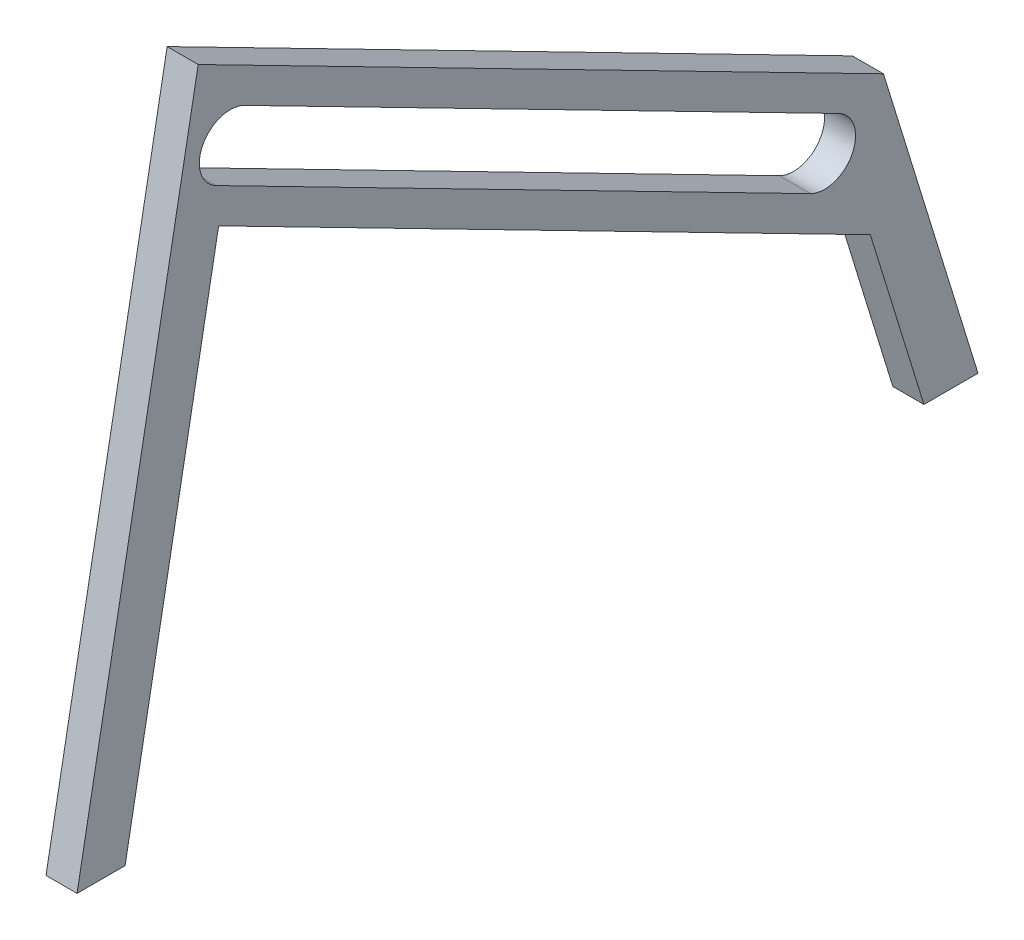
SolidWorks part; units mm, degrees
ref_plane "Front Plane" through (0, 0, 0) normal (0, 0, 1) x (1, 0, 0)
ref_plane "Top Plane" through (0, 0, 0) normal (0, 1, 0) x (1, 0, 0)
ref_plane "Right Plane" through (0, 0, 0) normal (1, 0, 0) x (0, 0, -1)
sketch "Sketch1" plane through (0, 0, 0) normal (1, 0, 0) x (0, 0, -1)
  line L0 (-444.5, 0) -> (444.5, 0) construction
  line L1 (-444.5, 0) -> (-394.9465, 268.859) construction
  line L2 (-394.9465, 268.859) -> (-444.5, 0)
  line L3 (-394.9465, 268.859) -> (-114.6521, 125.4156)
  line L4 (-394.9465, 268.859) -> (-394.9465, 0) construction
  line L9 (-114.6521, 125.4156) -> (-75.9791, 0)
  line L10 (-254.7993, 197.1373) -> (-306.6298, 95.8584) construction
  line L16 (-306.6298, 95.8584) -> (-454.2509, 171.4049) construction
  line L17 (-306.6298, 95.8584) -> (-85.4714, -17.3216) construction
  line L18 (-394.9465, 0) -> (-394.9465, -231.14) construction
  line L19 (-260.585, 185.8317) -> (-302.8069, 207.4392) construction
  line L20 (-272.1565, 163.2207) -> (-316.6941, 186.0132) construction
  line L21 (-277.9422, 151.9151) -> (-386.5959, 207.5197)
  line L22 (-277.9422, 151.9151) -> (-120.015, 71.0943)
  line L23 (-419.7233, 134.4295) -> (-381.7028, 127.4219) construction
  line L24 (-400.713, 130.9257) -> (-424.844, 0) construction
  line L25 (-400.713, 130.9257) -> (-386.5959, 207.5197) construction
  line L26 (-386.5959, 207.5197) -> (-424.844, 0)
  line L27 (-98.0924, 0) -> (-120.015, 71.0943)
  line L28 (-293.905, 202.8836) -> (-305.4765, 180.2725) construction
  line L29 (-299.6907, 191.578) -> (-381.7903, 233.5933) construction
  line L30 (-299.6907, 191.578) -> (-138.7539, 109.2171) construction
  line L31 (-381.7903, 233.5933) -> (-138.7539, 109.2171) construction
  line L32 (-376.0046, 244.8988) -> (-132.9682, 120.5226)
  line L33 (-387.576, 222.2877) -> (-144.5397, 97.9115)
  line L34 (-444.5, 0) -> (-424.844, 0)
  line L35 (-98.0924, 0) -> (-75.9791, 0)
  line L36 (-384.1931, 220.5565) -> (-376.9847, 259.6669) construction
  arc A2 (-376.0046, 244.8988) -> (-387.576, 222.2877) centre (-381.7903, 233.5933) ccw
  arc A3 (-144.5397, 97.9115) -> (-132.9682, 120.5226) centre (-138.7539, 109.2171) ccw
  point P4 (0, 0)
  point P32 (-260.2721, 171.4052)
  dimension "D1" = 889
  dimension "D7" = 12.7
  dimension "D2" = 231.14
  dimension "D3" = 499.999
  dimension "D4" = 25.4
  dimension "D5" = 12.7
  dimension "D6" = 12.7
  dimension "D8" = 19.656
  dimension "D9" = 22.1133
extrude "Boss-Extrude1" add sketch "Sketch1" along normal blind 12.7
